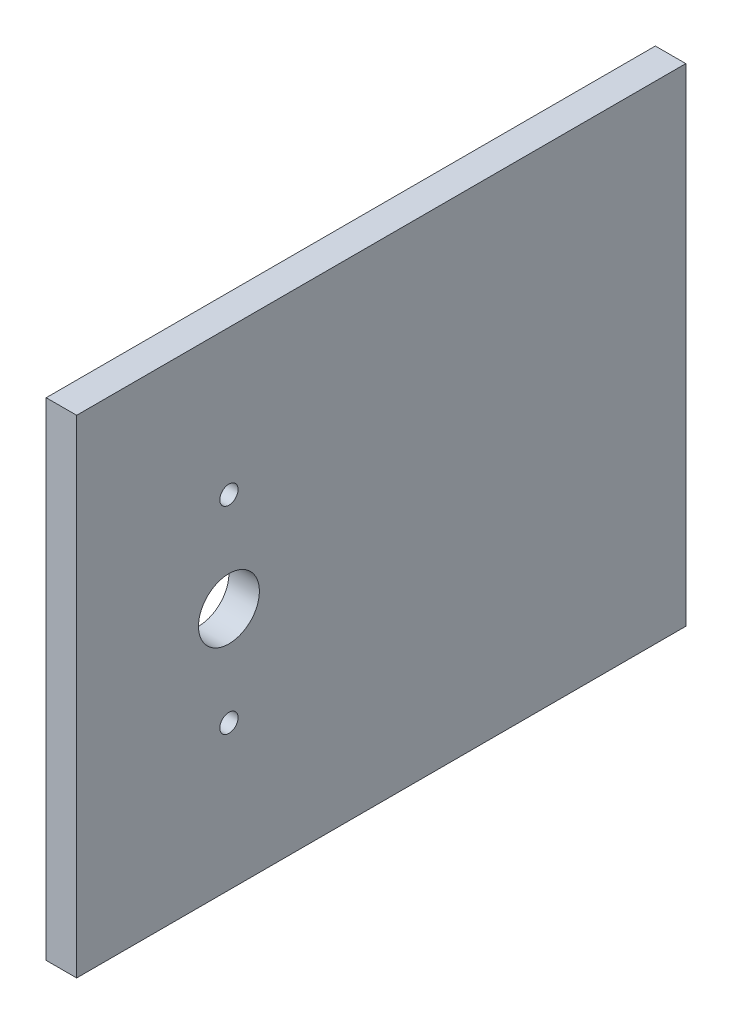
SolidWorks part; units mm, degrees
ref_plane "Front Plane" through (0, 0, 0) normal (1, 0, 0) x (0, 1, 0)
ref_plane "Top Plane" through (0, 0, 0) normal (0, 0, 1) x (0, 1, 0)
ref_plane "Right Plane" through (0, 0, 0) normal (0, 1, 0) x (-1, 0, 0)
sketch "Sketch1" plane through (0, 0, 0) normal (1, 0, 0) x (0, 1, 0)
  line L0 (-40, 25) -> (40, 25) construction
  line L1 (-40, -50) -> (40, -50)
  line L2 (-40, -50) -> (-40, 50)
  line L3 (-40, 50) -> (40, 50)
  line L4 (40, -50) -> (40, 50)
  line L5 (-40, -50) -> (40, 50) construction
  line L6 (-40, 50) -> (40, -50) construction
  line L7 (0, 50) -> (0, -50) construction
  circle A5 centre (0, 25) radius 5
  circle A6 centre (-16.22, 25) radius 1.5
  circle A7 centre (16.22, 25) radius 1.5
  point P0 (0, 0)
  dimension "D5" = 3
  dimension "D4" = 16.22
  dimension "D8" = 10
  dimension "D1" = 100
  dimension "D2" = 80
  dimension "D3" = 75
extrude "Boss-Extrude1" add sketch "Sketch1" along normal blind 5
